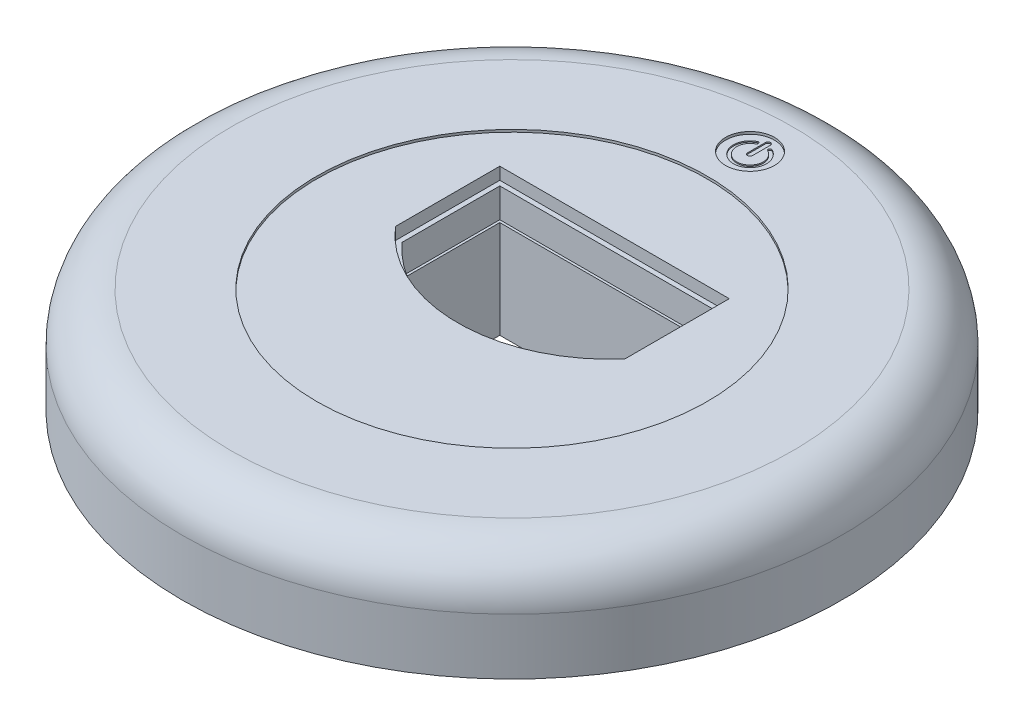
SolidWorks part; units mm, degrees
ref_plane "Alzado" through (0, 0, 0) normal (0, 0, 1) x (1, 0, 0)
ref_plane "Planta" through (0, 0, 0) normal (0, 1, 0) x (1, 0, 0)
ref_plane "Vista lateral" through (0, 0, 0) normal (1, 0, 0) x (0, 0, -1)
sketch "Croquis1" plane through (0, 0, 0) normal (0, 1, 0) x (1, 0, 0)
  circle A0 centre (0, 0) radius 135
extrude "Saliente-Extruir1" add sketch "Croquis1" along normal blind 43
sketch "Croquis2" plane through (0, 0, 0) normal (0, -1, 0) x (-1, 0, 0)
  circle A0 centre (0, 0) radius 133
  circle A1 centre (0, 0) radius 135
fillet "Redondeo5" radius 20 1 edges at (0, 43, 135)
extrude "Cortar-Extruir6" cut sketch "Croquis2" against normal blind 25 contours A0
fillet "Redondeo6" radius 25 1 edges at (0, 25, -133)
sketch "Croquis4" plane through (0, 43, 0) normal (0, 1, 0) x (1, 0, 0)
  circle A0 centre (0, 0) radius 80
extrude "Cortar-Extruir7" cut sketch "Croquis4" against normal blind 1
sketch "Croquis5" plane through (0, 42, 0) normal (0, 1, 0) x (1, 0, 0)
  line L2 (-45, 0) -> (-45, 40)
  line L3 (-45, 40) -> (45, 40)
  line L4 (45, 40) -> (45, 0)
  arc A0 (-45, 0) -> (45, 0) centre (0, 40) ccw
extrude "Cortar-Extruir8" cut sketch "Croquis5" against normal blind 67 contours L2 A0 L4 L3 region at (0, 42, -12.6855)
sketch "Croquis6" plane through (0, 43, 0) normal (0, 1, 0) x (1, 0, 0)
  circle A2 centre (0, 97.5) radius 10
extrude "Cortar-Extruir9" cut sketch "Croquis6" against normal blind 1 contours A2
sketch "Croquis7" plane through (0, 42, 0) normal (0, 1, 0) x (1, 0, 0)
  line L5 (-1, 97.5) -> (-1, 104.8467)
  line L6 (1, 97.5) -> (1, 104.8467)
  arc A0 (-3.0255, 103.5417) -> (2.9242, 103.5914) centre (0, 97.5) ccw
  arc A1 (-2.4305, 102.3536) -> (2.3491, 102.3935) centre (0, 97.5) ccw
  arc A2 (-2.4305, 102.3536) -> (-3.0255, 103.5417) centre (-2.728, 102.9476) ccw
  arc A3 (2.9242, 103.5914) -> (2.3491, 102.3935) centre (2.6367, 102.9924) ccw
  arc A4 (-1, 97.5) -> (1, 97.5) centre (0, 97.5) ccw
  arc A5 (1, 104.8467) -> (-1, 104.8467) centre (0, 104.8467) ccw
extrude "Cortar-Extruir10" cut sketch "Croquis7" against normal blind 0.5 contours A5 L5 A4 L6 | A1 A3 A0 A2
sketch "Croquis9" plane through (0, 25, 0) normal (0, -1, 0) x (1, 0, 0)
  line L0 (45, -40) -> (-45, -40)
  line L1 (-45, -40) -> (-45, 0)
  line L2 (45, -40) -> (45, 0)
  line L6 (44, -39) -> (-44, -39)
  line L7 (-44, -39) -> (-44, -0.382)
  line L8 (44, -39) -> (44, -0.382)
  arc A0 (45, 0) -> (-45, 0) centre (0, -40) ccw
  arc A2 (44, -0.382) -> (-44, -0.382) centre (0, -40) ccw
  dimension "D1" = 1
extrude "Saliente-Extruir3" add sketch "Croquis9" along normal blind 40 separate body
sketch "Croquis11" plane through (0, 25, 0) normal (0, -1, 0) x (1, 0, 0)
  line L9 (-45, 0) -> (-45, -40)
  line L10 (-45, -40) -> (45, -40)
  line L11 (45, -40) -> (45, 0)
  line L12 (-47, -42) -> (47, -42)
  line L13 (47, -42) -> (47, 0.7533)
  line L14 (-47, 0.7533) -> (-47, -42)
  line L15 (-47, -42) -> (47, -42)
  line L16 (47, -42) -> (47, 0.7533)
  line L17 (-47, 0.7533) -> (-47, -42)
  circle A2 centre (0, 0) radius 107
  circle A3 centre (0, 0) radius 107
  arc A6 (45, 0) -> (-45, 0) centre (0, -40) ccw
  arc A7 (47, 0.7533) -> (-47, 0.7533) centre (0, -40) ccw
  arc A8 (47, 0.7533) -> (-47, 0.7533) centre (0, -40) ccw
  line M11 (45, -40) -> (-45, -40)
  line M12 (-45, -40) -> (-45, 0)
  arc M13 (-45, 0) -> (45, 0) centre (0, -40) cw
  line M14 (45, 0) -> (45, -40)
  dimension "D1" = 1
  dimension "D2" = 2
  dimension "D3" = 2
extrude "Saliente-Extruir4" add sketch "Croquis11" along normal blind 5 contours L16 A8 L17 L15 M14 M11 M12 M13 region at (-45.8616, 25, -20.6233)
sketch "Croquis12" plane through (0, 42, 0) normal (0, 1, 0) x (1, 0, 0)
  line L18 (45, 40) -> (-45, 40)
  line L19 (-45, 40) -> (-45, 0)
  line L20 (45, 0) -> (45, 40)
  line L21 (47, -0.7533) -> (47, 42)
  line L22 (-47, 42) -> (-47, -0.7533)
  line L23 (47, 42) -> (-47, 42)
  line L24 (47, -0.7533) -> (47, 42)
  line L25 (-47, 42) -> (-47, -0.7533)
  line L26 (47, 42) -> (-47, 42)
  circle A2 centre (0, 0) radius 78
  circle A3 centre (0, 0) radius 78
  arc A7 (-45, 0) -> (45, 0) centre (0, 40) ccw
  arc A8 (-47, -0.7533) -> (47, -0.7533) centre (0, 40) ccw
  arc A9 (-47, -0.7533) -> (47, -0.7533) centre (0, 40) ccw
  dimension "D1" = 2
  dimension "D2" = 2
  dimension "D3" = 2
extrude "Cortar-Extruir11" cut sketch "Croquis12" against normal blind 5 contours L25 A9 L24 L26 | L18 L19 A7 L20
